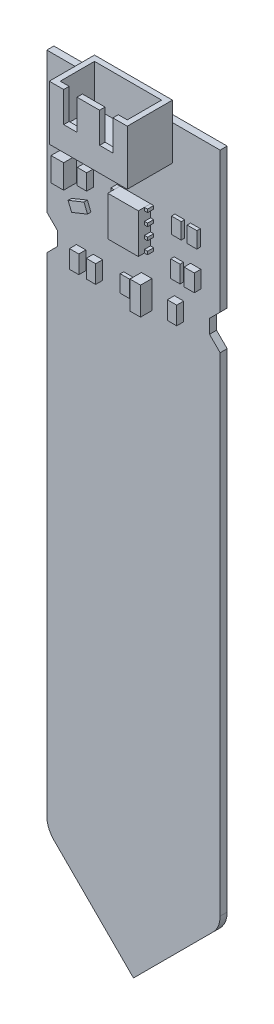
SolidWorks part; units mm, degrees
other "Camera1"
material "Plain Carbon Steel"
ref_plane "Front" through (0, 0, 0) normal (0, 0, 1) x (1, 0, 0)
ref_plane "Top" through (0, 0, 0) normal (0, 1, 0) x (1, 0, 0)
ref_plane "Right" through (0, 0, 0) normal (1, 0, 0) x (0, 0, -1)
ref_axis "X-Axis" through (0, 0, 0) along (1, 0, 0)
ref_axis "Y-Axis" through (0, 0, 0) along (0, 1, 0)
ref_axis "Z-Axis" through (0, 0, 0) along (0, 0, 1)
sketch "Sketch1" plane through (0, 0, 0) normal (0, 0, 1) x (1, 0, 0)
  line L0 (-11.1125, 0) -> (11.1125, 0)
  line L1 (11.1125, 0) -> (11.1125, -18)
  line L2 (-11.1125, 0) -> (-11.1125, -18)
  line L3 (-11.1125, -18) -> (-9.75, -19.3625)
  line L4 (-9.75, -19.3625) -> (-9.75, -21.1375)
  line L5 (-9.75, -21.1375) -> (-11.1125, -22.5)
  line L6 (-11.1125, -22.5) -> (-11.1125, -85.0724)
  line L7 (-10.1826, -87.3174) -> (0, -97.5)
  line L8 (0, -97.5) -> (10.1826, -87.3174)
  line L9 (11.1125, -85.0724) -> (11.1125, -22.5)
  line L10 (11.1125, -22.5) -> (9.75, -21.1375)
  line L11 (9.75, -21.1375) -> (9.75, -19.3625)
  line L12 (9.75, -19.3625) -> (11.1125, -18)
  line L13 (0, 0) -> (0, -97.5) construction
  arc A0 (10.1826, -87.3174) -> (11.1125, -85.0724) centre (7.9375, -85.0724) ccw
  arc A1 (-11.1125, -85.0724) -> (-10.1826, -87.3174) centre (-7.9375, -85.0724) ccw
  dimension "D2" = 3.175
  dimension "D1" = 22.225
  dimension "D3" = 19.5
  dimension "D4" = 18
  dimension "D5" = 4.5
  dimension "D6" = 97.5
extrude "Boss-Extrude1" add sketch "Sketch1" along normal blind 0.9
sketch "Sketch2" plane through (0, 0, 0.9) normal (0, 0, 1) x (1, 0, 0)
  line L0 (11.1125, 0) -> (-11.1125, 0) construction
  line L1 (-7.3125, -22) -> (-6.1125, -22)
  line L2 (-7.3125, -22) -> (-7.3125, -19.7)
  line L3 (-7.3125, -19.7) -> (-6.1125, -19.7)
  line L4 (-6.1125, -22) -> (-6.1125, -19.7)
  line L5 (-5.1525, -22) -> (-3.9525, -22)
  line L6 (-5.1525, -22) -> (-5.1525, -19.7)
  line L7 (-5.1525, -19.7) -> (-3.9525, -19.7)
  line L8 (-3.9525, -22) -> (-3.9525, -19.7)
  line L9 (-11.1125, 0) -> (-11.1125, -18) construction
  line L10 (11.1125, -18) -> (11.1125, 0) construction
  line L11 (-1.2675, -21.86) -> (-0.0675, -21.86)
  line L12 (-1.2675, -21.86) -> (-1.2675, -19.7)
  line L13 (-1.2675, -19.7) -> (-0.0675, -19.7)
  line L14 (-0.0675, -21.86) -> (-0.0675, -19.7)
  line L15 (1.0125, -22.2) -> (2.3625, -22.2)
  line L16 (1.0125, -22.2) -> (1.0125, -18.64)
  line L17 (1.0125, -18.64) -> (2.3625, -18.64)
  line L18 (2.3625, -22.2) -> (2.3625, -18.64)
  line L19 (5.2425, -21.4) -> (6.4425, -21.4)
  line L20 (5.2425, -21.4) -> (5.2425, -19.1)
  line L21 (5.2425, -19.1) -> (6.4425, -19.1)
  line L22 (6.4425, -21.4) -> (6.4425, -19.1)
  line L23 (-7.4957, -16) -> (-5.4576, -15.1717)
  line L24 (-8.9225, -9.79) -> (-7.3125, -9.79)
  line L25 (-8.9225, -9.79) -> (-8.9225, -12.84)
  line L26 (-8.9225, -12.84) -> (-7.3125, -12.84)
  line L27 (-7.3125, -9.79) -> (-7.3125, -12.84)
  line L28 (-6.3125, -10.18) -> (-5.1125, -10.18)
  line L29 (-6.3125, -10.18) -> (-6.3125, -12.22)
  line L30 (-6.3125, -12.22) -> (-5.1125, -12.22)
  line L31 (-5.1125, -10.18) -> (-5.1125, -12.22)
  line L32 (-1.7225, -10.42) -> (2.1875, -10.42)
  line L33 (-1.7225, -10.42) -> (-1.7225, -15.5)
  line L34 (-1.7225, -15.5) -> (2.1875, -15.5)
  line L35 (2.1875, -10.42) -> (2.1875, -15.5)
  line L36 (5.3125, -10) -> (6.5625, -10)
  line L37 (5.3125, -10) -> (5.3125, -12.05)
  line L38 (5.3125, -12.05) -> (6.5625, -12.05)
  line L39 (6.5625, -10) -> (6.5625, -12.05)
  line L40 (7.3125, -10) -> (8.5625, -10)
  line L41 (7.3125, -10) -> (7.3125, -12.05)
  line L42 (7.3125, -12.05) -> (8.5625, -12.05)
  line L43 (8.5625, -10) -> (8.5625, -12.05)
  line L44 (5.2125, -14.8) -> (6.4125, -14.8)
  line L45 (5.2125, -14.8) -> (5.2125, -17)
  line L46 (5.2125, -17) -> (6.4125, -17)
  line L47 (6.4125, -14.8) -> (6.4125, -17)
  line L48 (7.3125, -14.47) -> (8.6325, -14.47)
  line L49 (7.3125, -14.47) -> (7.3125, -16.67)
  line L50 (7.3125, -16.67) -> (8.6325, -16.67)
  line L51 (8.6325, -14.47) -> (8.6325, -16.67)
  line L52 (-7.4957, -16) -> (-7.9475, -14.8883)
  line L53 (-5.4576, -15.1717) -> (-5.9094, -14.06)
  line L54 (-7.9475, -14.8883) -> (-5.9094, -14.06)
  dimension "D1" = 22
  dimension "D2" = 1.2
  dimension "D3" = 2.3
  dimension "D4" = 5
  dimension "D5" = 2.16
  dimension "D6" = 2.16
  dimension "D7" = 1.2
  dimension "D8" = 1.35
  dimension "D9" = 3.56
  dimension "D10" = 0.2
  dimension "D11" = 10.1
  dimension "D12" = 12.38
  dimension "D13" = 5.87
  dimension "D14" = 21.4
  dimension "D15" = 1.61
  dimension "D16" = 3.05
  dimension "D17" = 2.04
  dimension "D18" = 1.2
  dimension "D19" = 5.08
  dimension "D20" = 3.91
  dimension "D21" = 1.32
  dimension "D22" = 1.25
  dimension "D23" = 1.2
  dimension "D24" = 1.25
  dimension "D25" = 2.05
  dimension "D26" = 12.05
  dimension "D27" = 3.8
  dimension "D28" = 5.8
  dimension "D29" = 2.2
  dimension "D30" = 17
  dimension "D31" = 5.9
  dimension "D32" = 3.8
  dimension "D33" = 16.67
  dimension "D34" = 13.3
  dimension "D35" = 15.5
  dimension "D36" = 12.84
  dimension "D37" = 3.8
  dimension "D38" = 12.22
  dimension "D39" = 6
  dimension "D40" = 2.2
  dimension "D41" = 1.2
  dimension "D42" = 16
  dimension "D43" = 14.06
  dimension "D44" = 19.06
extrude "Boss-Extrude2" add sketch "Sketch2" along normal blind 1.57 separate body contours L32 L35 L34 L33
extrude "Boss-Extrude3" add sketch "Sketch2<3>" along normal blind 0.44 separate body contours L43 L40 L41 L42 | L39 L36 L37 L38 | L47 L44 L45 L46 | L54 L52 L23 L53 | L11 L14 L13 L12 region at (-0.6675, -20.78, 0.9) region at (-6.7025, -15.03, 0.9) region at (5.9375, -11.025, 0.9) region at (7.9375, -11.025, 0.9) region at (5.8125, -15.9, 0.9)
sketch "Sketch2<3>" plane through (0, 0, 0.9) normal (0, 0, 1) x (1, 0, 0) same geometry as "Sketch2"
extrude "Boss-Extrude4" add sketch "Sketch2<4>" along normal blind 1.65 separate body contours L27 L24 L25 L26 region at (-8.1175, -11.315, 0.9)
sketch "Sketch2<4>" plane through (0, 0, 0.9) normal (0, 0, 1) x (1, 0, 0) same geometry as "Sketch2"
extrude "Boss-Extrude5" add sketch "Sketch2<5>" along normal blind 0.9 separate body contours L1 L4 L3 L2 | L5 L8 L7 L6 | L31 L28 L29 L30 | L19 L22 L21 L20 region at (-6.7125, -20.85, 0.9) region at (-4.5525, -20.85, 0.9) region at (5.8425, -20.25, 0.9) region at (-5.7125, -11.2, 0.9)
sketch "Sketch2<5>" plane through (0, 0, 0.9) normal (0, 0, 1) x (1, 0, 0) same geometry as "Sketch2"
extrude "Boss-Extrude6" add sketch "Sketch2<6>" along normal blind 1.46 separate body contours L15 L18 L17 L16 region at (1.6875, -20.42, 0.9)
sketch "Sketch2<6>" plane through (0, 0, 0.9) normal (0, 0, 1) x (1, 0, 0) same geometry as "Sketch2"
extrude "Boss-Extrude7" add sketch "Sketch2<7>" along normal blind 0.83 separate body contours L51 L48 L49 L50 region at (7.9725, -15.57, 0.9)
sketch "Sketch2<7>" plane through (0, 0, 0.9) normal (0, 0, 1) x (1, 0, 0) same geometry as "Sketch2"
sketch "Sketch4" plane through (0, 0, 0.9) normal (0, 0, 1) x (1, 0, 0)
  line L0 (11.1125, 0) -> (-11.1125, 0) construction
  line L1 (-5, -4.5) -> (5, -4.5)
  line L2 (-5, -4.5) -> (-5, 2.5)
  line L3 (-5, 2.5) -> (5, 2.5)
  line L4 (5, -4.5) -> (5, 2.5)
  line L5 (0, 0) -> (0, 2.5) construction
  dimension "D1" = 10
  dimension "D2" = 7
  dimension "D3" = 2.5
extrude "Boss-Extrude8" add sketch "Sketch4" along normal blind 5.8 separate body
shell "Shell1" thickness 0.7 removed face at (0, 2.5, 3.8)
sketch "Sketch5" plane through (0, 0, 6.7) normal (0, 0, 1) x (1, 0, 0)
  line L0 (5, 2.5) -> (-5, 2.5) construction
  line L1 (-3.15, 2.5) -> (-1.45, 2.5)
  line L2 (-3.15, 2.5) -> (-3.15, -1.4)
  line L3 (-3.15, -1.4) -> (-1.45, -1.4)
  line L4 (-1.45, 2.5) -> (-1.45, -1.4)
  line L5 (-1.45, -1.4) -> (1.45, -1.4) construction
  line L6 (1.45, 2.5) -> (3.15, 2.5)
  line L7 (1.45, 2.5) -> (1.45, -1.4)
  line L8 (1.45, -1.4) -> (3.15, -1.4)
  line L9 (3.15, 2.5) -> (3.15, -1.4)
  line L10 (0, 0) -> (0, -1.4) construction
  line L11 (5, -4.5) -> (5, 2.5) construction
  dimension "D1" = 2.9
  dimension "D2" = 1.85
  dimension "D3" = 3.9
extrude "Cut-Extrude1" cut sketch "Sketch5" against normal up to next (0.7 mm away)
sketch "Sketch6" plane through (0, 0, 0) normal (0, 0, -1) x (-1, 0, 0)
  line L0 (-2.19, -4.5) -> (-0.35, -4.5) construction
  line L1 (-2.89, -4.15) -> (-2.19, -4.15)
  line L2 (-2.89, -4.15) -> (-2.89, -4.85)
  line L3 (-2.89, -4.85) -> (-2.19, -4.85)
  line L4 (-2.19, -4.15) -> (-2.19, -4.85)
  line L5 (-0.35, -4.15) -> (0.35, -4.15)
  line L6 (-0.35, -4.15) -> (-0.35, -4.85)
  line L7 (-0.35, -4.85) -> (0.35, -4.85)
  line L8 (0.35, -4.15) -> (0.35, -4.85)
  line L9 (2.19, -4.15) -> (2.89, -4.15)
  line L10 (2.19, -4.15) -> (2.19, -4.85)
  line L11 (2.19, -4.85) -> (2.89, -4.85)
  line L12 (2.89, -4.15) -> (2.89, -4.85)
  line L13 (0.35, -4.5) -> (2.19, -4.5) construction
  line L14 (0, -4.15) -> (0, 0) construction
  line L15 (-11.1125, 0) -> (11.1125, 0) construction
  dimension "D1" = 0.7
  dimension "D2" = 2.54
  dimension "D3" = 4.5
extrude "Boss-Extrude9" add sketch "Sketch6" along normal blind 2.5 separate body
ref_plane "Plane1" through (0, 0, 1.685) normal (0, 0, -1) x (-1, 0, 0)
sketch "Sketch7" plane through (0, 0, 1.685) normal (0, 0, -1) x (-1, 0, 0)
  line L0 (-2.1875, -10.42) -> (-2.1875, -15.5) construction
  line L1 (-2.1875, -15.5) -> (-2.5875, -15.5)
  line L2 (-2.1875, -15.5) -> (-2.1875, -15.1)
  line L3 (-2.1875, -15.1) -> (-2.5875, -15.1)
  line L4 (-2.5875, -15.5) -> (-2.5875, -15.1)
  line L5 (-2.1875, -13.94) -> (-2.5875, -13.94)
  line L6 (-2.1875, -13.94) -> (-2.1875, -13.54)
  line L7 (-2.1875, -13.54) -> (-2.5875, -13.54)
  line L8 (-2.5875, -13.94) -> (-2.5875, -13.54)
  line L9 (-2.1875, -10.82) -> (-2.1875, -11.98) construction
  line L10 (-2.1875, -12.38) -> (-2.5875, -12.38)
  line L11 (-2.1875, -12.38) -> (-2.1875, -11.98)
  line L12 (-2.1875, -11.98) -> (-2.5875, -11.98)
  line L13 (-2.5875, -12.38) -> (-2.5875, -11.98)
  line L14 (-2.1875, -10.42) -> (-2.5875, -10.42)
  line L15 (-2.1875, -10.42) -> (-2.1875, -10.82)
  line L16 (-2.1875, -10.82) -> (-2.5875, -10.82)
  line L17 (-2.5875, -10.42) -> (-2.5875, -10.82)
  line L18 (-2.1875, -12.38) -> (-2.1875, -13.54) construction
  line L19 (-2.1875, -13.94) -> (-2.1875, -15.1) construction
  dimension "D1" = 0.4
extrude "Boss-Extrude10" add sketch "Sketch7" along normal up to surface (0.785 mm away) separate body up to face at (0.2325, -12.96, 0.9)
ref_plane "Plane2" through (0.2325, 0, 0) normal (1, 0, 0) x (0, 0, -1)
mirror "Mirror1" about plane through (0.2325, 0, 0) normal (1, 0, 0) of bodies 120 121 122 123
